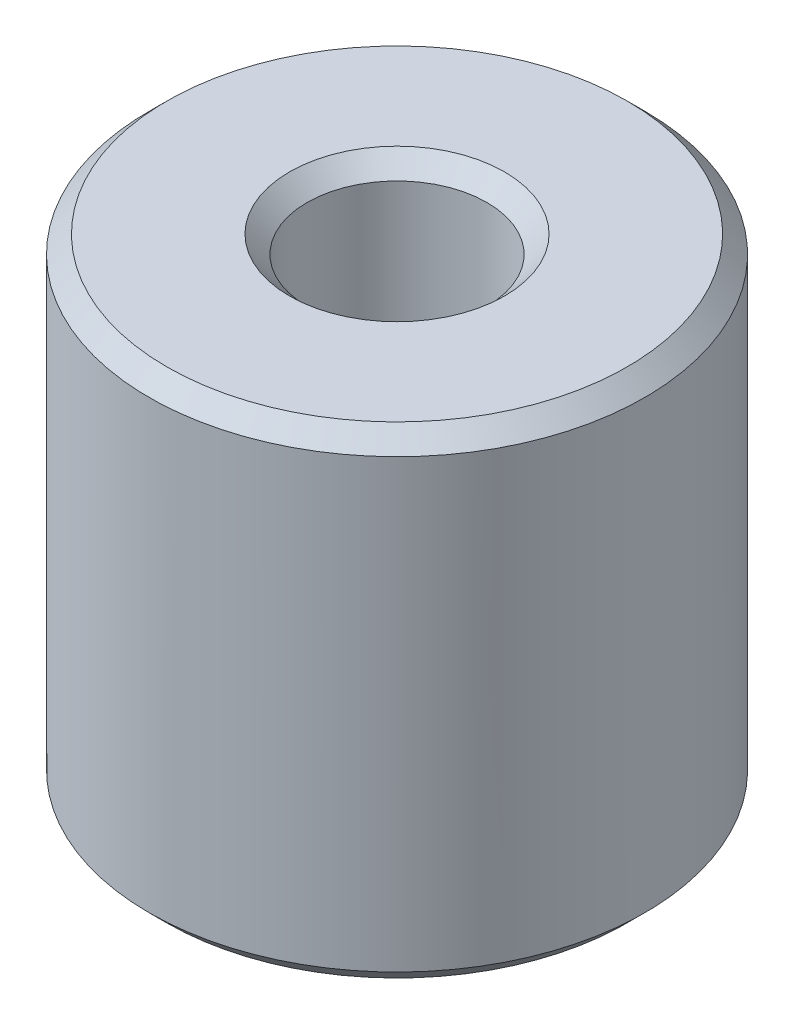
SolidWorks part; units mm, degrees
ref_plane "Front Plane" through (0, 0, 0) normal (0, 0, 1) x (1, 0, 0)
ref_plane "Top Plane" through (0, 0, 0) normal (0, 1, 0) x (1, 0, 0)
ref_plane "Right Plane" through (0, 0, 0) normal (1, 0, 0) x (0, 0, -1)
sketch "Sketch1" plane through (0, 0, 0) normal (0, 1, 0) x (1, 0, 0)
  circle A0 centre (0, 0) radius 15
  dimension "SLEEVE_OD" = 30
extrude "Boss-Extrude1" add sketch "Sketch1" along normal blind 29.1415
sketch "Sketch2" plane through (0, 0, 0) normal (0, 1, 0) x (1, 0, 0)
  circle A0 centre (0, 0) radius 5.4394
  dimension "BORE_D" = 10.8788
extrude "Cut-Extrude1" cut sketch "Sketch2" along normal through all
chamfer "Chamfer1" distance 1.0681 angle 45 4 edges at (0, 29.1415, 5.4394) (0, 0, 5.4394) (0, 0, 15) (0, 29.1415, 15)
